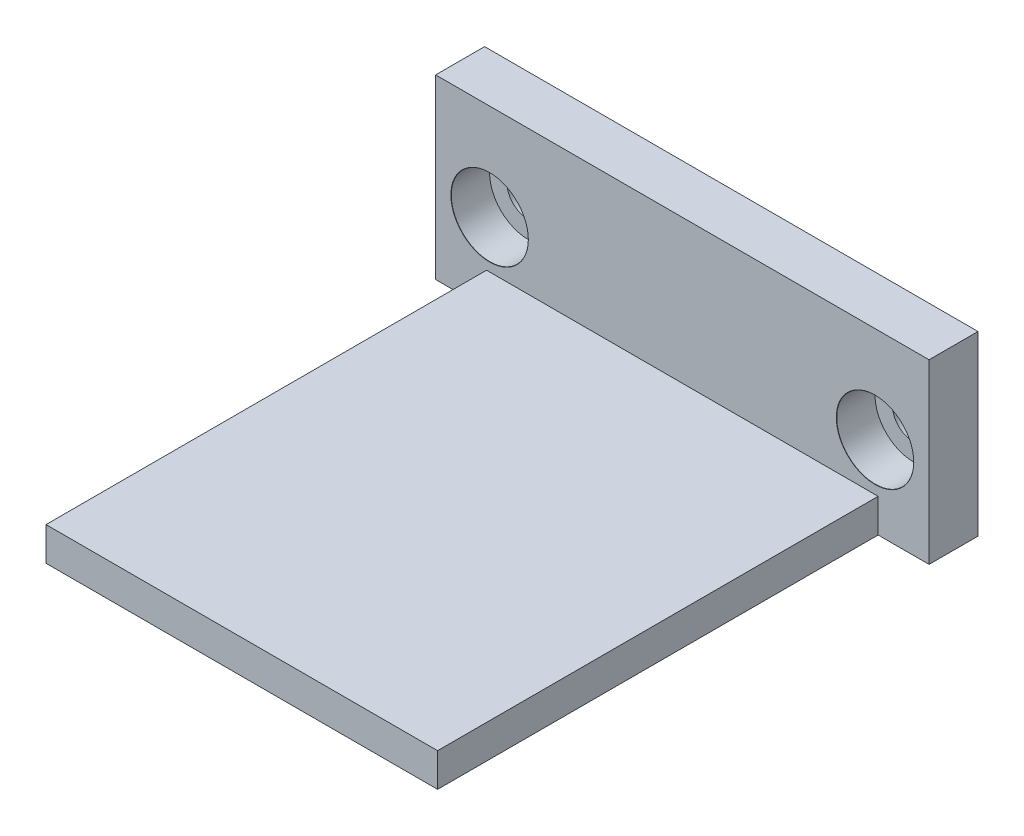
SolidWorks part; units mm, degrees
ref_plane "Front" through (0, 0, 0) normal (0, 0, 1) x (1, 0, 0)
ref_plane "Top" through (0, 0, 0) normal (0, 1, 0) x (1, 0, 0)
ref_plane "Right" through (0, 0, 0) normal (1, 0, 0) x (0, 0, -1)
sketch "Sketch1" plane through (0, 0, 0) normal (0, 0, 1) x (1, 0, 0)
  line L1 (0, 0) -> (64.008, 0)
  line L2 (0, 0) -> (0, 24.9936)
  line L3 (0, 24.9936) -> (64.008, 24.9936)
  line L4 (64.008, 0) -> (64.008, 24.9936)
  dimension "D1" = 24.9936
  dimension "D2" = 64.008
extrude "Boss-Extrude1" add sketch "Sketch1" along normal blind 6.35
sketch "Sketch2" plane through (0, 0, 6.35) normal (0, 0, 1) x (1, 0, 0)
  line L0 (64.008, 0) -> (64.008, 24.9936) construction
  line L1 (0, 0) -> (64.008, 0)
  line L2 (0, 0) -> (0, 6.35)
  line L3 (0, 6.35) -> (64.008, 6.35)
  line L4 (64.008, 0) -> (64.008, 6.35)
  dimension "D1" = 6.35
extrude "Boss-Extrude2" add sketch "Sketch2" along normal blind 57.15
sketch "Sketch5" plane through (0, 0, 6.35) normal (0, 0, 1) x (1, 0, 0)
  line L0 (-2.4403, 12.5) -> (65.3922, 12.5) construction
  line L1 (0, 0) -> (64.008, 0) construction
  line L2 (7, 27.9859) -> (7, -6.3192) construction
  line L3 (57, 30.103) -> (57, -4.1589) construction
  line L4 (0, 24.9936) -> (0, 6.35) construction
  dimension "D1" = 12.5
  dimension "D2" = 50
  dimension "D3" = 7
hole_wizard "CBORE for M5 SHCS1" positions "Sketch6" profile "Sketch7" counterbore size "M5" standard "ANSI Metric" end condition up to next
sketch "Sketch6" plane through (0, 0, 6.35) normal (0, 0, 1) x (1, 0, 0)
  line L0 (-2.4403, 12.5) -> (65.3922, 12.5) construction
  line L1 (7, 27.9859) -> (7, -6.3192) construction
  line L2 (57, 30.103) -> (57, -4.1589) construction
  point P0 (7, 12.5)
  point P6 (57, 12.5)
sketch "Sketch7" plane through (7, 12.5, 6.35) normal (1, 0, 0) x (0, -1, 0)
  line L0 (0, 0) -> (0, 6.35)
  line L1 (0, 6.35) -> (2.75, 6.35)
  line L3 (2.75, 6.35) -> (2.75, 5)
  line L4 (5, 5) -> (2.75, 5)
  line L5 (5, 5) -> (5, 0.025)
  line L6 (5, 0.025) -> (5.025, 0)
  line L7 (5.025, 0) -> (0, 0)
  line L8 (-5, 0.025) -> (-5.025, 0) construction
  line L11 (0, -6.35) -> (0, 107.95) construction
  dimension "Thru Hole Dia." = 5.5
  dimension "Thru Hole Depth" = 6.35
  dimension "C'Bore Dia." = 10
  dimension "C'Bore Depth" = 5
  dimension "Near C'Sink Dia." = 10.05
  dimension "Near C'Sink Angle" = 90
sketch "Sketch8" plane through (0, 0, 63.5) normal (0, 0, 1) x (1, 0, 0)
  line L0 (0, 0) -> (64.008, 0) construction
  line L1 (0, 6.35) -> (6.604, 6.35)
  line L2 (0, 6.35) -> (0, 0)
  line L3 (0, 0) -> (6.604, 0)
  line L4 (6.604, 6.35) -> (6.604, 0)
  line L6 (64.008, 6.35) -> (57.404, 6.35)
  line L7 (64.008, 6.35) -> (64.008, 0)
  line L8 (64.008, 0) -> (57.404, 0)
  line L9 (57.404, 6.35) -> (57.404, 0)
  dimension "D1" = 6.604
  dimension "D2" = 6.604
extrude "Cut-Extrude1" cut sketch "Sketch8" against normal up to surface (57.15 mm away) up to face at (12.025, 12.5, 6.35)
sketch "Sketch9" plane through (0, 0, 6.35) normal (0, 0, 1) x (1, 0, 0)
  line L0 (64.008, 0) -> (64.008, 24.9936) construction
  line L1 (0, 0) -> (64.008, 0)
  line L2 (0, 0) -> (0, 2)
  line L3 (0, 2) -> (64.008, 2)
  line L4 (64.008, 0) -> (64.008, 2)
  dimension "D1" = 2
extrude "Cut-Extrude2" cut sketch "Sketch9" against normal through all both and the other way through all
